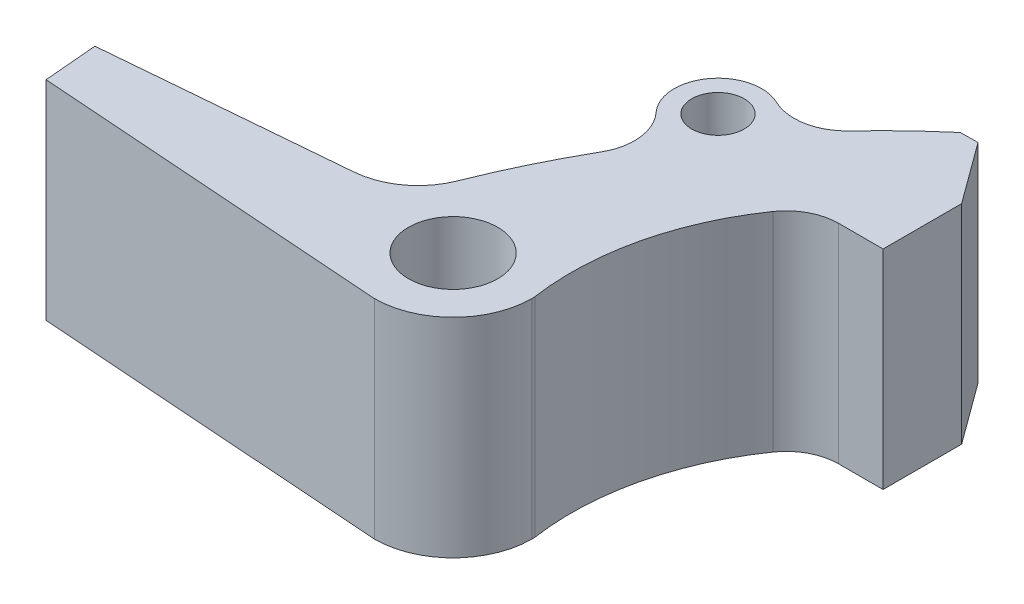
SolidWorks part; units mm, degrees
ref_plane "Front Plane" through (0, 0, 0) normal (0, 0, 1) x (1, 0, 0)
ref_plane "Top Plane" through (0, 0, 0) normal (0, 1, 0) x (1, 0, 0)
ref_plane "Right Plane" through (0, 0, 0) normal (1, 0, 0) x (0, 0, -1)
sketch "Sketch1" plane through (0, 0, 0) normal (0, 1, 0) x (1, 0, 0)
  line L0 (8.5487, 20.4395) -> (9.5487, 20.4464)
  line L1 (9.5487, 20.4464) -> (12.1033, 16.9577)
  line L2 (12.1033, 16.9577) -> (12.1033, 12.4704)
  line L3 (12.1033, 12.4704) -> (9.5684, 12.4704)
  line L4 (-6.7942, 1.168) -> (-20.4349, -0.0084)
  line L5 (-20.4349, -0.0084) -> (-20.1714, -3.0642)
  line L6 (-20.1714, -3.0642) -> (0.0246, -4.5084)
  circle A0 centre (0.0246, -0.0084) radius 2.55
  arc A1 (-4.2369, 1.437) -> (-4.2535, 1.3871) centre (0.0246, -0.0084) ccw
  arc A2 (4.5215, 0.1583) -> (7.1031, 11.1799) centre (19.7626, 2.4016) cw
  arc A3 (8.5487, 20.4395) -> (5.2794, 17.3277) centre (36.4213, -12.1168) ccw
  arc A4 (4.5215, 0.1583) -> (4.5246, -0.0084) centre (33.2407, 0.6072) ccw
  arc A5 (9.5684, 12.4704) -> (7.1031, 11.1799) centre (9.5684, 9.4704) ccw
  arc A6 (-0.6157, -4.4627) -> (4.5215, 0.1583) centre (0.0246, -0.0084) ccw
  arc A7 (-3.4195, 3.6789) -> (-6.7942, 1.168) centre (-7.1379, 5.1532) cw
  circle A8 centre (0.7075, 14.4362) radius 1.5
  arc A9 (1.7948, 16.6873) -> (-1.1351, 12.7466) centre (0.7075, 14.4362) ccw
  arc A10 (-0.7447, 9.2252) -> (-3.4195, 3.6789) centre (36.4213, -12.1168) ccw
  arc A11 (1.7948, 16.6873) -> (5.2794, 17.3277) centre (3.0995, 19.3888) ccw
  arc A12 (-1.1351, 12.7466) -> (-0.7447, 9.2252) centre (-3.3463, 10.7191) cw
  dimension "D1" = 9
  dimension "D3" = 3
  dimension "D4" = 4
  dimension "D5" = 3
  dimension "D6" = 5
  dimension "D7" = 3
  dimension "D2" = 1
  dimension "D8" = 0
extrude "Boss-Extrude1" add sketch "Sketch1" along normal blind 11.9 contours A9 A12 A10 A7 L4 L5 L6 A6 A4 A2 A5 L3 L2 L1 L0 A3 A11 A0 A8 region at (-0.9303, 0, -5.8221)
ref_plane "Plane1" through (0, 5.59, 0) normal (0, 1, 0) x (1, 0, 0)
sketch "Sketch2" plane through (0, 5.59, 0) normal (0, 1, 0) x (1, 0, 0)
  circle A0 centre (0.7075, 14.4362) radius 4
extrude "Cut-Extrude1" cut sketch "Sketch2" against normal mid plane 6
fillet "Fillet1" radius 10 2 edges at (-0.3496, 5.59, -10.5784) (4.0974, 5.59, -16.5596)
